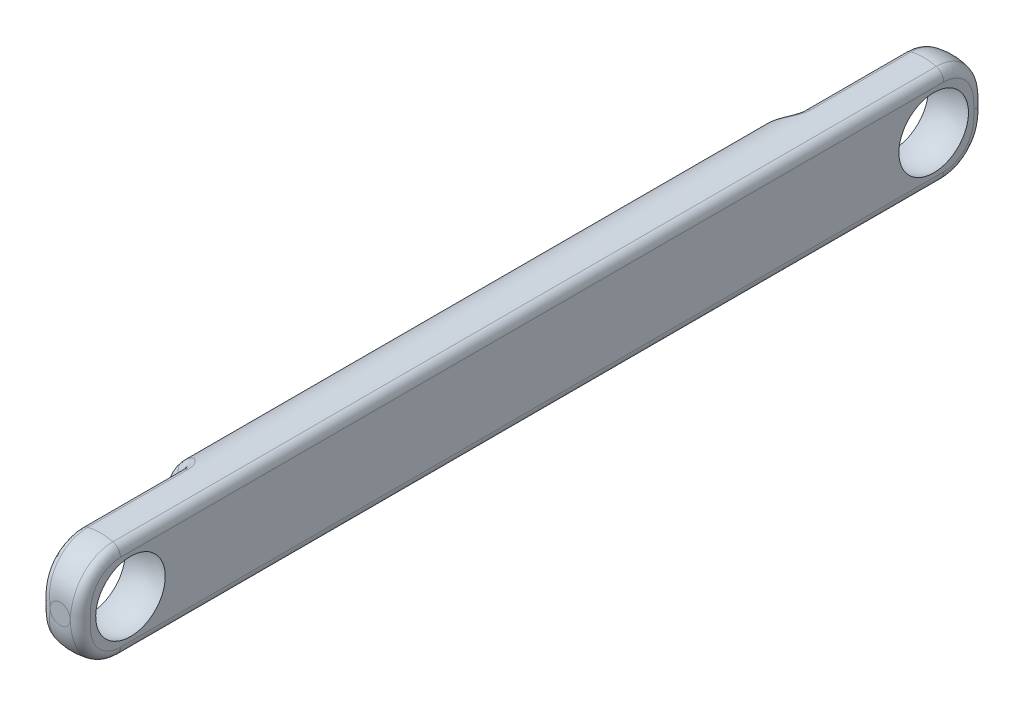
SolidWorks part; units mm, degrees
ref_plane "Plan de face" through (0, 0, 0) normal (0, 0, 1) x (1, 0, 0)
ref_plane "Plan de dessus" through (0, 0, 0) normal (0, 1, 0) x (1, 0, 0)
ref_plane "Plan de droite" through (0, 0, 0) normal (1, 0, 0) x (0, 0, -1)
sketch "Esquisse1" plane through (0, 0, 0) normal (0, 0, 1) x (1, 0, 0)
  circle A0 centre (0, 0) radius 5
  dimension "D1" = 10
extrude "Extrusion1" add sketch "Esquisse1" along normal blind 90
sketch "Esquisse2" plane through (0, 0, 90) normal (0, 0, 1) x (1, 0, 0)
  line L0 (-2, 4.5826) -> (-2, -4.5826)
  line L1 (-2, -4.5826) -> (-5, -4.5826)
  line L2 (-5, -4.5826) -> (-5, 4.5826)
  line L3 (-5, 4.5826) -> (-2, 4.5826)
  line L4 (2, 4.5826) -> (5, 4.5826)
  line L5 (5, 4.5826) -> (5, -4.5826)
  line L6 (5, -4.5826) -> (2, -4.5826)
  line L7 (2, -4.5826) -> (2, 4.5826)
  line L8 (2, 4.5826) -> (-2, -4.5826) construction
  circle A0 centre (0, 0) radius 5 construction
  dimension "D1" = 4
extrude "Extrusion2" cut sketch "Esquisse2" against normal blind 15
sketch "Esquisse3" plane through (0, 0, 0) normal (0, 0, -1) x (-1, 0, 0)
  line L0 (-2, 4.5826) -> (-2, -4.5826)
  line L1 (-2, -4.5826) -> (-5, -4.5826)
  line L2 (-5, -4.5826) -> (-5, 4.5826)
  line L3 (-5, 4.5826) -> (-2, 4.5826)
  line L4 (2, 4.5826) -> (5, 4.5826)
  line L5 (5, 4.5826) -> (5, -4.5826)
  line L6 (5, -4.5826) -> (2, -4.5826)
  line L7 (2, -4.5826) -> (2, 4.5826)
  line L8 (2, -4.5826) -> (-2, 4.5826) construction
  line L9 (0, 0) -> (0, -7.5138) construction
  circle A0 centre (0, 0) radius 5 construction
  dimension "D2" = 4
extrude "Extrusion3" cut sketch "Esquisse3" against normal blind 15
ref_plane "Plan1" through (0, 0, 0) normal (1, 0, 0) x (0, 0, -1)
sketch "Esquisse4" plane through (0, 0, 0) normal (1, 0, 0) x (0, 0, -1)
  line L0 (-89, 0) -> (-81, 0)
  line L1 (-85, 0) -> (-82.5, 0) construction
  line L2 (-90, 4.5826) -> (-75, -4.5826) construction
  line L3 (-90, 4.5826) -> (-90, -4.5826) construction
  arc A0 (-81, 0) -> (-89, 0) centre (-85, 0) ccw
  dimension "D1" = 8
  dimension "D2" = 5
revolve "Enlèvement de matière-Révolution1" cut sketch "Esquisse4" angle 360 about L0
ref_plane "Plan2" through (0, 0, 0) normal (1, 0, 0) x (0, 0, -1)
sketch "Esquisse5" plane through (0, 0, 0) normal (1, 0, 0) x (0, 0, -1)
  line L0 (-15, -4.5826) -> (0, 4.5826) construction
  line L1 (-9, 0) -> (-1, 0)
  line L2 (-5, 0) -> (-7.5, 0) construction
  line L3 (0, -4.5826) -> (0, 4.5826) construction
  arc A0 (-1, 0) -> (-9, 0) centre (-5, 0) ccw
  dimension "D1" = 8
  dimension "D2" = 5
revolve "Enlèvement de matière-Révolution2" cut sketch "Esquisse5" angle 360 about L1
ref_plane "Plan3" through (0, 0, 15) normal (0, 0, -1) x (-1, 0, 0)
sketch "Esquisse6" plane through (0, 0, 15) normal (0, 0, -1) x (-1, 0, 0)
  line L0 (-2, -9.798) -> (-2, 9.798)
  line L2 (-2, -4.5826) -> (-2, 4.5826) construction
  arc A0 (-2, 9.798) -> (-2, -9.798) centre (0, 0) ccw
  dimension "D1" = 20
extrude "Extrusion4" cut sketch "Esquisse6" against normal up to surface (60 mm away) up to face at (3.5, 0, 75)
fillet "Congé1" radius 4 2 edges at (0, -5, 0) (0, -5, 90)
fillet "Congé2" radius 1 14 edges at (-2, 4.5826, 9.5) (-2, -4.5826, 9.5) (-2, -4.5826, 80.5) (-2, 4.5826, 80.5) (-5, 0, 15) (-2, 0, 15) (-2, 0, 75) (-5, 0, 75) (2, -1.6635, 0.3345) (2, 4.5826, 45) (2, 1.6635, 89.6655) (-2, 1.6635, 0.3345) (-2, -1.6635, 89.6655) (2, -4.5826, 45)
